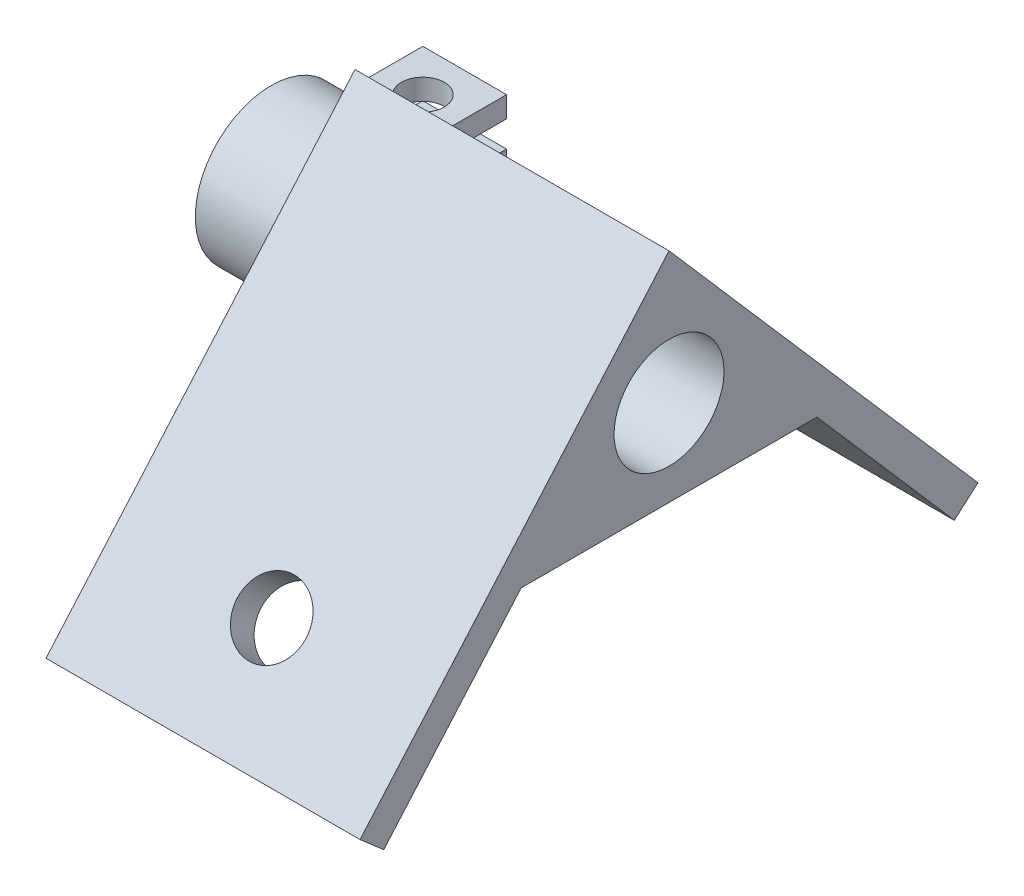
SolidWorks part; units mm, degrees
material "PLA Black"
ref_plane "Front" through (0, 0, 0) normal (0, 0, 1) x (1, 0, 0)
ref_plane "Top" through (0, 0, 0) normal (0, 1, 0) x (1, 0, 0)
ref_plane "Right" through (0, 0, 0) normal (1, 0, 0) x (0, 0, -1)
sketch "Sketch1" plane through (0, 0, 0) normal (1, 0, 0) x (0, 0, -1)
  line L0 (0, 12.5751) -> (-29.5132, -21.376)
  line L1 (-29.5132, -21.376) -> (-27.2491, -23.3442)
  line L2 (-27.2491, -23.3442) -> (-14.1279, -8.25)
  line L3 (-14.1279, -8.25) -> (14.1279, -8.25)
  line L4 (0, 31.2499) -> (0, -31.1028) construction
  line L5 (27.2491, -23.3442) -> (14.1279, -8.25)
  line L6 (0, 12.5751) -> (29.5132, -21.376)
  line L7 (29.5132, -21.376) -> (27.2491, -23.3442)
  circle A0 centre (0, 0) radius 5.25
  dimension "D1" = 10.5
  dimension "D4" = 3
  dimension "D2" = 41
  dimension "D3" = 3
  dimension "D5" = 3
  dimension "D6" = 20
extrude "Boss-Extrude1" add sketch "Sketch1" along normal mid plane 30
hole_wizard "M6 Clearance Hole1" positions "Sketch3" profile "Sketch4" hole size "M6" standard "DIN" end condition through all
sketch "Sketch3" plane through (0, 3.4443, 3.9622) normal (0, -0.6561, -0.7547) x (-1, 0, 0)
  line L0 (-34.564, -25.4951) -> (6.8322, -25.4951) construction
  line L2 (0, -15.4951) -> (0, -35.4951) construction
  line L3 (-15, -15.4951) -> (15, -15.4951) construction
  line L4 (-15, -35.4951) -> (15, -35.4951) construction
  point P0 (0, -25.4951)
sketch "Sketch4" plane through (0, -15.7971, 20.6885) normal (1, 0, 0) x (0, 0.7547, -0.6561)
  line L0 (0, 0) -> (0, 25.2739)
  line L1 (0, 25.2739) -> (3.3, 25.2739)
  line L2 (3.3, 25.2739) -> (3.3, 0)
  line L5 (3.3, 0) -> (0, 0)
  line L11 (0, -6.35) -> (0, 107.95) construction
  dimension "Thru Hole Dia." = 6.6
  dimension "Thru Hole Depth" = 25.2739
mirror "Mirror1" about plane through (0, 0, 0) normal (0, 0, 1) of "M6 Clearance Hole1"
sketch "Sketch5" plane through (-15, 0, 0) normal (-1, 0, 0) x (0, 0, 1)
  line L0 (-5.099, 1.25) -> (-14.4807, 1.25)
  line L1 (-14.4807, 1.25) -> (-14.4807, 3.25)
  line L2 (-14.4807, 3.25) -> (-6.4807, 3.25)
  line L3 (0, 0) -> (-16.2155, 0) construction
  line L4 (-6.4807, -3.25) -> (-6.4807, -10.25)
  line L5 (-14.4807, -1.25) -> (-14.4807, -10.25)
  line L6 (-5.099, -1.25) -> (-14.4807, -1.25)
  line L7 (-6.4807, -10.25) -> (-14.4807, -10.25)
  circle A0 centre (0, 0) radius 5.25 construction
  arc A1 (-6.4807, 3.25) -> (-6.4807, -3.25) centre (0, 0) cw
  arc A2 (-5.099, 1.25) -> (-5.099, -1.25) centre (0, 0) cw
  dimension "D1" = 2
  dimension "D2" = 8
  dimension "D3" = 2.5
  dimension "D4" = 2
  dimension "D5" = 9
extrude "Boss-Extrude2" add sketch "Sketch5" along normal blind 8
sketch "Sketch6" plane through (0, 3.25, 0) normal (0, 1, 0) x (1, 0, 0)
  line L0 (-19, 14.4807) -> (-19, 6.4807) construction
  line L1 (-23, 14.4807) -> (-15, 14.4807) construction
  line L2 (-23, 6.4807) -> (-15, 6.4807) construction
  circle A0 centre (-19, 10.4807) radius 2.05
  dimension "D1" = 4.1
extrude "Cut-Extrude1" cut sketch "Sketch6" against normal through all
